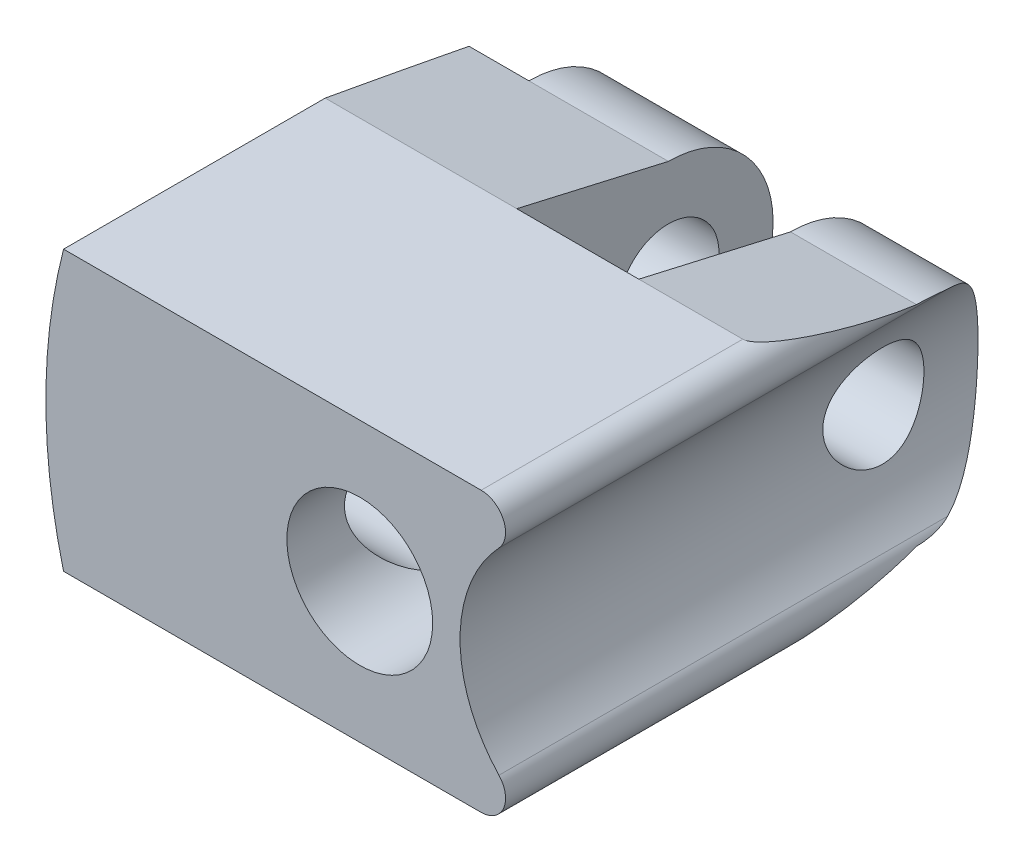
SolidWorks part; units mm, degrees
note: The reader was unsure of these and kept them because the rebuilt part matched: shared geometry of "Schizzo7<4>".
ref_plane "Piano frontale" through (0, 0, 0) normal (0, 0, 1) x (1, 0, 0)
ref_plane "Piano superiore" through (0, 0, 0) normal (0, 1, 0) x (1, 0, 0)
ref_plane "Piano destro" through (0, 0, 0) normal (1, 0, 0) x (0, 0, -1)
sketch "Schizzo1" plane through (0, 0, 0) normal (0, 0, 1) x (1, 0, 0)
  line L0 (5.9922, -4) -> (-8.4919, -4)
  line L2 (-8.4919, 4) -> (5.9922, 4)
  circle A0 centre (0, 0) radius 2.09
  circle A1 centre (7, 0) radius 4.125 construction
  circle A2 centre (7, 0) radius 16 construction
  arc A3 (5.9922, 4) -> (5.9922, -4) centre (7, 0) ccw
  arc A4 (-8.4919, 4) -> (-8.4919, -4) centre (7, 0) ccw
  point P8 (0, 0)
  point P12 (0, 0)
  dimension "D1" = 4.18
  dimension "D3" = 8.25
  dimension "D4" = 32
  dimension "D2" = 7
  dimension "D5" = 8
extrude "Estrusione-Estrusione1" add sketch "Schizzo1" along normal blind 15
sketch "Schizzo5" plane through (0, -4, 0) normal (0, -1, 0) x (1, 0, 0)
  line L0 (-8.4919, 0) -> (5.9922, 0) construction
  line L1 (0.5001, 0) -> (-2.9999, 0)
  line L2 (0.5001, 0) -> (0.5001, 7.5)
  line L3 (0.5001, 7.5) -> (-2.9999, 7.5)
  line L4 (-2.9999, 0) -> (-2.9999, 7.5)
  point P6 (-1.2499, 7.5)
  point P7 (-1.2499, 0)
  dimension "D1" = 3.5
  dimension "D2" = 7.5
extrude "Taglio-Estrusione4" cut sketch "Schizzo5" against normal through all
sketch "Schizzo6" plane through (0.5001, 0, 0) normal (-1, 0, 0) x (0, 0, 1)
  line L0 (0, 4) -> (7.5, 4) construction
  line L1 (0, -4) -> (6, -4)
  line L2 (0, -4) -> (0, 4)
  line L3 (0, 4) -> (6, 4)
  line L4 (6, -4) -> (6, 4)
  dimension "D1" = 6
extrude "Estrusione-Estrusione2" add sketch "Schizzo6" against normal up to next
sketch "Schizzo7" plane through (-2.9999, 0, 0) normal (1, 0, 0) x (0, 0, -1)
  line L0 (-7.5, 4) -> (-7.5, -4) construction
  line L1 (0, 4) -> (0, -4) construction
  circle A0 centre (-3.15, 0) radius 1.45
  circle A1 centre (-11.5, 0) radius 1.85
  dimension "D1" = 3.7
  dimension "D2" = 2.9
  dimension "D3" = 4
  dimension "D4" = 3.15
extrude "Taglio-Estrusione5" cut sketch "Schizzo7" against normal through all and the other way through all contours A0
extrude "Taglio-Estrusione6" cut sketch "Schizzo7<4>" against normal through all and the other way up to next contours A1
sketch "Schizzo7<4>" plane through (-2.9999, 0, 0) normal (1, 0, 0) x (0, 0, -1) same geometry as "Schizzo7"
fillet "Raccordo1" radius 0.7 1 edges at (5.9922, 4, 7.5)
fillet "Raccordo2" radius 0.7 1 edges at (5.9922, -4, 7.5)
sketch "Schizzo8" plane through (-2.9999, 0, 0) normal (1, 0, 0) x (0, 0, -1)
  line L1 (-7.5, -4) -> (0, -4) construction
  line L2 (-3.15, -4) -> (0, -4)
  line L3 (0, -4) -> (0, 4)
  line L4 (0, 4) -> (-3.15, 4)
  line L5 (-7.5, 4) -> (0, 4) construction
  line L7 (-3.15, -3) -> (-7.5, -4)
  line L8 (-7.5, -4) -> (-3.15, -4)
  line L9 (-3.15, 3) -> (-7.5, 4)
  line L10 (-7.5, 4) -> (-3.15, 4)
  arc A0 (-3.15, -3) -> (-3.15, 3) centre (-3.15, 0) ccw
  dimension "D1" = 3
extrude "Taglio-Estrusione7" cut sketch "Schizzo8" against normal through all and the other way through all
sketch "Schizzo9" plane through (-2.9999, 0, 0) normal (1, 0, 0) x (0, 0, -1)
  circle A0 centre (-3.15, 0) radius 3
extrude "Taglio-Estrusione9" cut sketch "Schizzo9" against normal through all from offset 4
